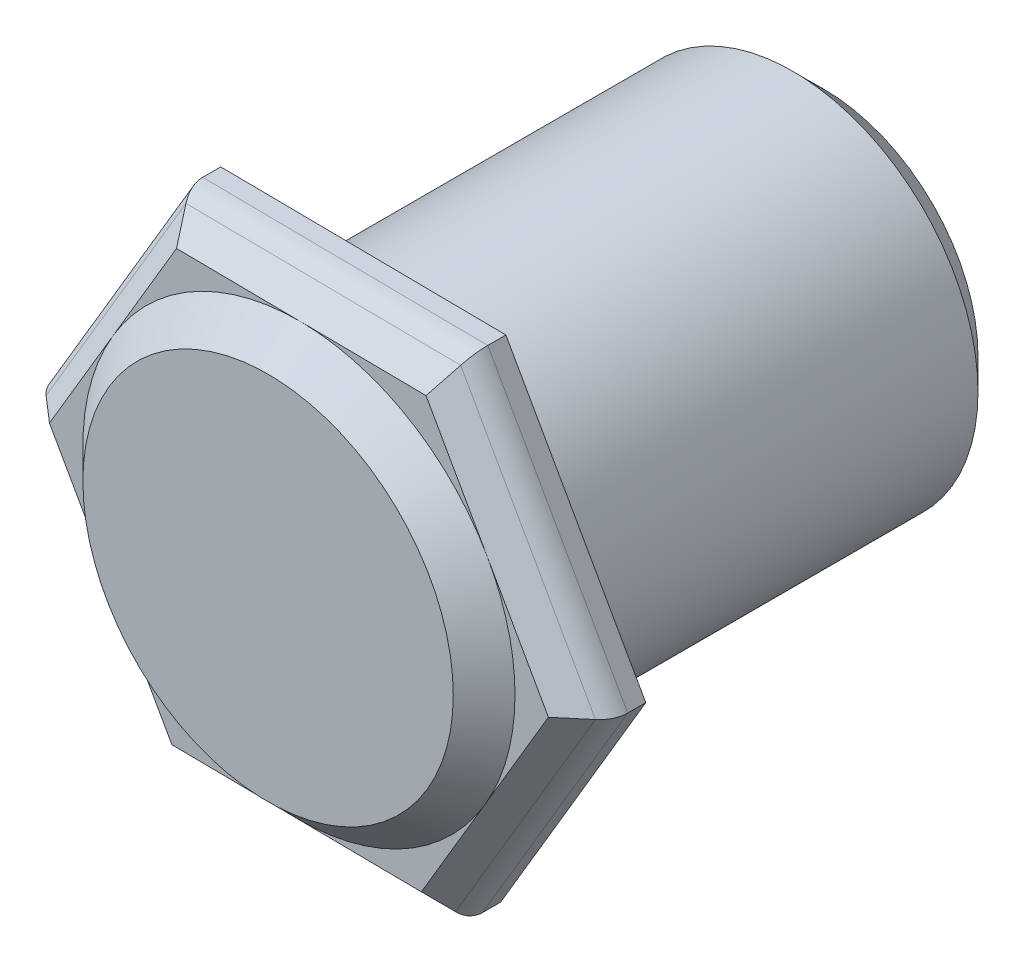
SolidWorks part; units mm, degrees
ref_plane "前视基准面" through (0, 0, 0) normal (0, 0, 1) x (1, 0, 0)
ref_plane "上视基准面" through (0, 0, 0) normal (0, 1, 0) x (1, 0, 0)
ref_plane "右视基准面" through (0, 0, 0) normal (1, 0, 0) x (0, 0, -1)
sketch "草图1" plane through (0, 0, 0) normal (0, 0, 1) x (1, 0, 0)
  circle A0 centre (0, 0) radius 6
  dimension "D1" = 12
extrude "凸台-拉伸1" add sketch "草图1" along normal blind 15
sketch "草图2" plane through (0, 0, 15) normal (0, 0, 1) x (1, 0, 0)
  line L1 (4.7038, 7.9503) -> (-4.5333, 8.0488)
  line L2 (-4.5333, 8.0488) -> (-9.2371, 0.0985)
  line L3 (-9.2371, 0.0985) -> (-4.7038, -7.9503)
  line L4 (-4.7038, -7.9503) -> (4.5333, -8.0488)
  line L5 (4.5333, -8.0488) -> (9.2371, -0.0985)
  line L6 (9.2371, -0.0985) -> (4.7038, 7.9503)
  circle A0 centre (0, 0) radius 8 construction
  dimension "D1" = 16
extrude "凸台-拉伸2" add sketch "草图2" along normal blind 2
sketch "草图3" plane through (0, 0, 17) normal (0, 0, 1) x (1, 0, 0)
  circle A0 centre (0, 0) radius 7
extrude "凸台-拉伸3" add sketch "草图3" along normal blind 1
chamfer "倒角1" distance 1 angle 45 8 edges at (-6.8852, 4.0736, 17) (0.0853, 7.9995, 17) (6.9704, 3.9259, 17) (6.8852, -4.0736, 17) (-6.9704, -3.9259, 17) (-0.0853, -7.9995, 17) (7, 0, 18) (6, 0, 0)
fillet "圆角1" radius 1 6 edges at (0.0853, 7.9995, 16) (6.9704, 3.9259, 16) (6.8852, -4.0736, 16) (-0.0853, -7.9995, 16) (-6.9704, -3.9259, 16) (-6.8852, 4.0736, 16)
sketch "草图4" plane through (0, 0, 0) normal (0, 0, -1) x (-1, 0, 0)
  circle A0 centre (0, 0) radius 5
extrude "切除-拉伸1" cut sketch "草图4" against normal blind 10
